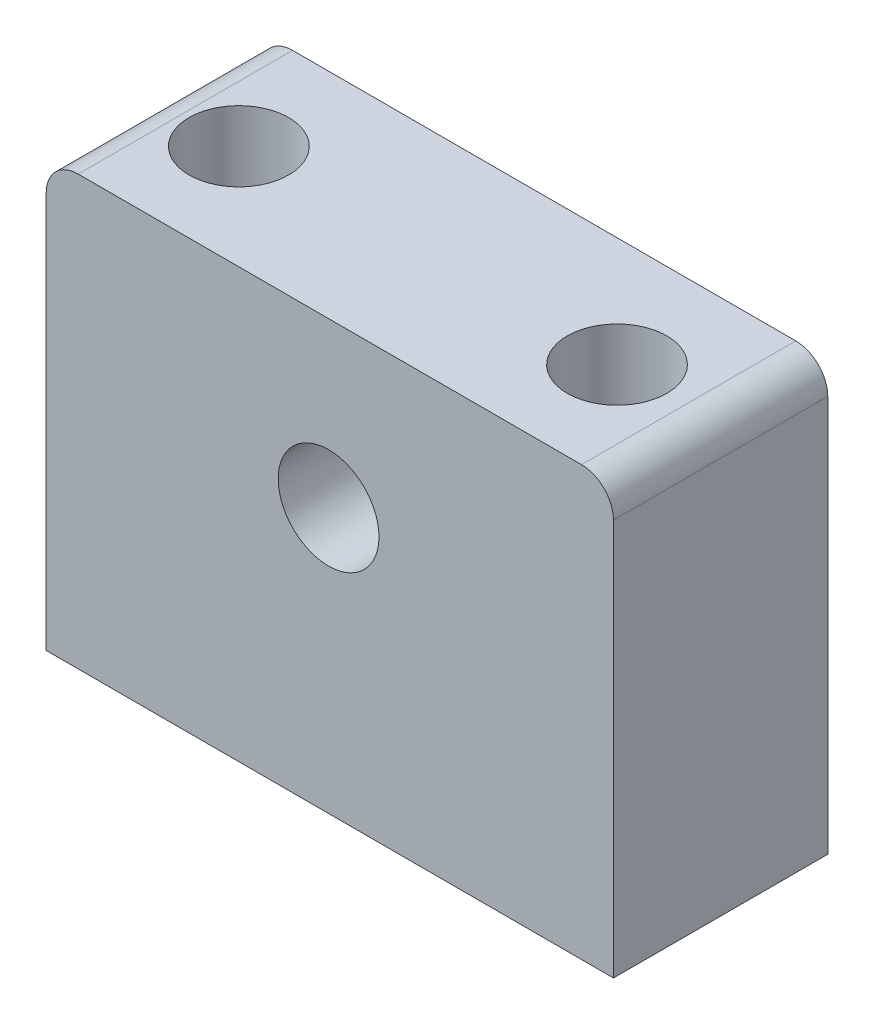
SolidWorks part; units mm, degrees
ref_plane "Front Plane" through (0, 0, 0) normal (0, 0, 1) x (1, 0, 0)
ref_plane "Top Plane" through (0, 0, 0) normal (0, 1, 0) x (1, 0, 0)
ref_plane "Right Plane" through (0, 0, 0) normal (1, 0, 0) x (0, 0, -1)
sketch "Sketch1" plane through (0, 0, 0) normal (0, 0, 1) x (1, 0, 0)
  line L1 (0, 0) -> (45, 0)
  line L2 (0, 0) -> (0, 34)
  line L3 (0, 34) -> (45, 34)
  line L4 (45, 0) -> (45, 34)
  circle A0 centre (22.4, 21) radius 4
  dimension "D3" = 8
  dimension "D1" = 45
  dimension "D2" = 34
  dimension "D4" = 13
  dimension "D5" = 22.4
extrude "Boss-Extrude1" add sketch "Sketch1" along normal blind 17
sketch "Sketch2" plane through (0, 34, 0) normal (0, 1, 0) x (1, 0, 0)
  line L0 (0, -17) -> (0, 0) construction
  circle A0 centre (7, -8.7186) radius 3.95
  circle A1 centre (37, -8.7186) radius 3.95
  dimension "D1" = 7.9
  dimension "D3" = 7.9
  dimension "D2" = 7
  dimension "D4" = 30
extrude "Cut-Extrude1" cut sketch "Sketch2" against normal blind 17
fillet "Fillet1" radius 2.54 2 edges at (0, 34, 8.5) (45, 34, 8.5)
